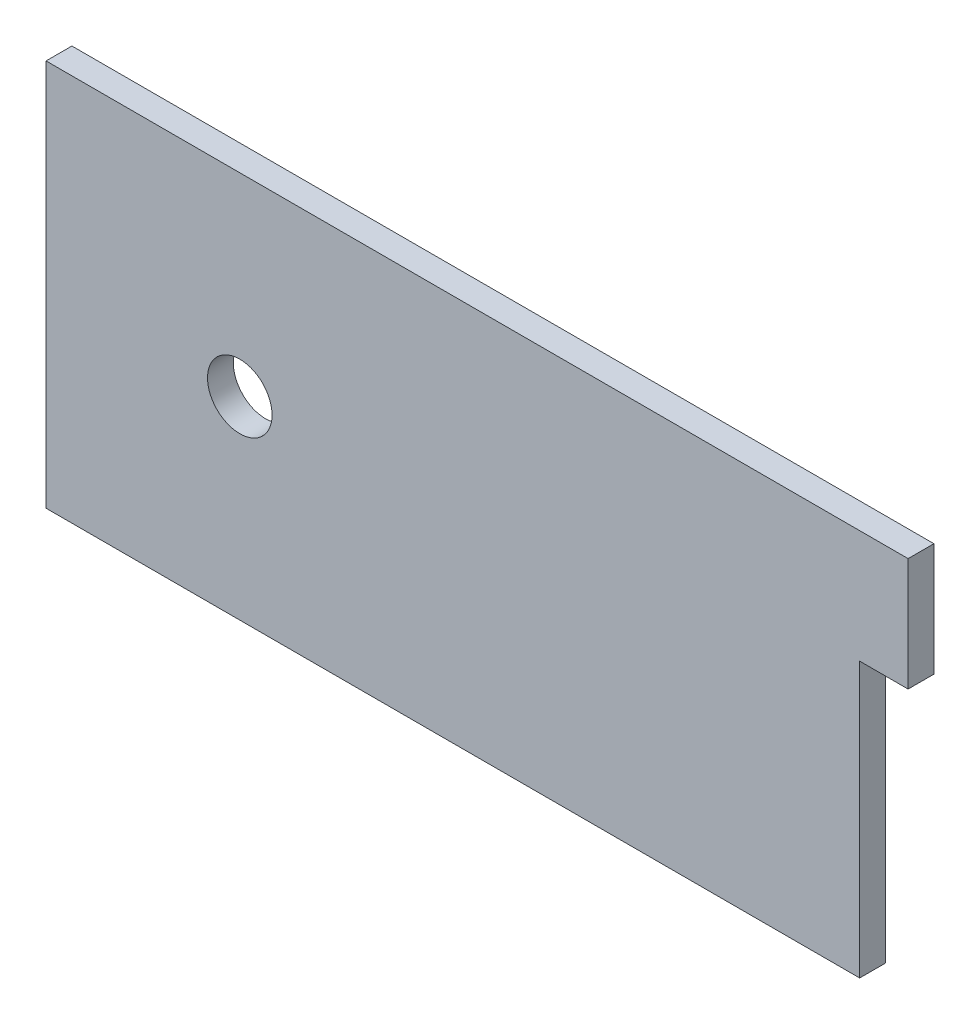
SolidWorks part; units mm, degrees
ref_plane "Front Plane" through (0, 0, 0) normal (0, 0, 1) x (1, 0, 0)
ref_plane "Top Plane" through (0, 0, 0) normal (0, 1, 0) x (1, 0, 0)
ref_plane "Right Plane" through (0, 0, 0) normal (1, 0, 0) x (0, 0, -1)
sketch "Sketch1" plane through (0, 0, 0) normal (0, 0, 1) x (1, 0, 0)
  line L0 (45, 30) -> (52.5, 30)
  line L1 (-81, -30) -> (45, -30)
  line L2 (-81, -30) -> (-81, 30)
  line L3 (-81, 30) -> (45, 30)
  line L4 (45, -30) -> (45, 30) construction
  line L5 (52.5, 30) -> (52.5, 12.5)
  line L6 (52.5, 12.5) -> (45, 12.5)
  line L13 (45, 12.5) -> (45, -30)
  circle A2 centre (-51, 0) radius 5
  point P1 (0, 0)
  point P8 (0, 0)
  point P9 (-81, 0)
  dimension "D3" = 17.5
  dimension "D4" = 7.5
  dimension "D1" = 30
  dimension "D2" = 60
  dimension "D8" = 51
  dimension "D9" = 45
extrude "Boss-Extrude1" add sketch "Sketch1" along normal blind 4
